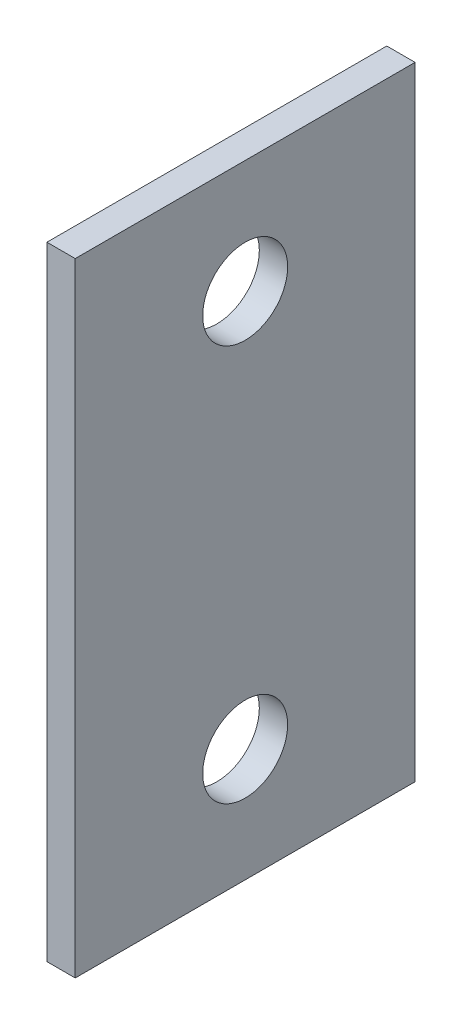
SolidWorks part; units mm, degrees
material "1023 Carbon Steel Sheet (SS)"
ref_plane "Front Plane" through (0, 0, 0) normal (0, 0, 1) x (1, 0, 0)
ref_plane "Top Plane" through (0, 0, 0) normal (0, 1, 0) x (1, 0, 0)
ref_plane "Right Plane" through (0, 0, 0) normal (1, 0, 0) x (0, 0, -1)
sketch "Sketch1" plane through (0, 0, 0) normal (1, 0, 0) x (0, 0, -1)
  line L0 (0, -22.225) -> (0, 22.225) construction
  line L1 (-19.05, -34.925) -> (19.05, -34.925)
  line L2 (-19.05, -34.925) -> (-19.05, 34.925)
  line L3 (-19.05, 34.925) -> (19.05, 34.925)
  line L4 (19.05, -34.925) -> (19.05, 34.925)
  line L5 (-19.05, -34.925) -> (19.05, 34.925) construction
  line L6 (-19.05, 34.925) -> (19.05, -34.925) construction
  circle A0 centre (0, 22.225) radius 4.7625
  circle A1 centre (0, -22.225) radius 4.7625
  point P0 (0, 0)
  point P9 (0, 0)
  dimension "D4" = 9.525
  dimension "D5" = 9.525
  dimension "D1" = 38.1
  dimension "D2" = 69.85
  dimension "D3" = 44.45
extrude "Boss-Extrude1" add sketch "Sketch1" along normal blind 3.175
